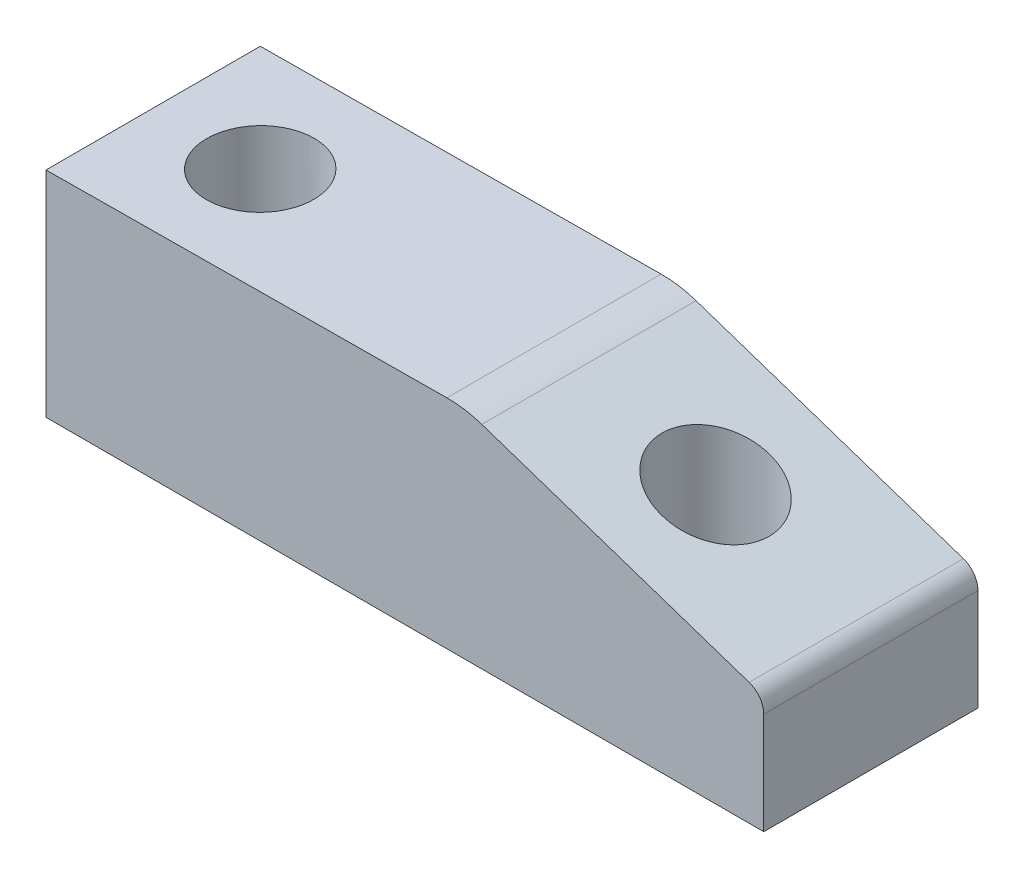
SolidWorks part; units mm, degrees
ref_plane "Front Plane" through (0, 0, 0) normal (0, 0, 1) x (1, 0, 0)
ref_plane "Top Plane" through (0, 0, 0) normal (0, 1, 0) x (1, 0, 0)
ref_plane "Right Plane" through (0, 0, 0) normal (1, 0, 0) x (0, 0, -1)
sketch "Sketch1" plane through (0, 0, 0) normal (0, 0, 1) x (1, 0, 0)
  line L0 (0, 0) -> (0, 40)
  line L2 (81.364, 39.5437) -> (131.2728, 22.7921)
  line L3 (134, 19) -> (134, 0)
  line L4 (134, 0) -> (0, 0)
  line L5 (0, 40) -> (74.8443, 40.5826)
  arc A1 (81.364, 39.5437) -> (74.8443, 40.5826) centre (75, 20.5832) ccw
  arc A2 (131.2728, 22.7921) -> (134, 19) centre (130, 19) cw
  dimension "D5" = 75
  dimension "D4" = 20
  dimension "D3" = 4
  dimension "D1" = 40
  dimension "D2" = 134
  dimension "D6" = 19
  dimension "D7" = 19
extrude "Boss-Extrude1" add sketch "Sketch1" along normal mid plane 40
sketch "Sketch4" plane through (0, 0, 0) normal (0, 1, 0) x (1, 0, 0)
  line L0 (74.8443, -20) -> (0, -20) construction
  line L1 (0, -20) -> (0, 20) construction
  line L2 (134, -20) -> (134, 20) construction
  circle A0 centre (20, 0) radius 10
  circle A1 centre (20, 0) radius 6
  circle A2 centre (105, 0) radius 6
  circle A3 centre (105, 0) radius 10
  point P12 (0, 0)
  dimension "D1" = 20
  dimension "D4" = 12
  dimension "D5" = 12
  dimension "D6" = 20
  dimension "D7" = 20
  dimension "D2" = 20
  dimension "D3" = 29
extrude "Cut-Extrude11" cut sketch "Sketch4" along normal through all contours A1 | A2 region at (20, 0, 0) region at (105, 0, 0)
extrude "Cut-Extrude12" cut sketch "Sketch4<13>" along normal through all from offset 10
sketch "Sketch4<13>" plane through (0, 0, 0) normal (0, 1, 0) x (1, 0, 0) same geometry as "Sketch4"
